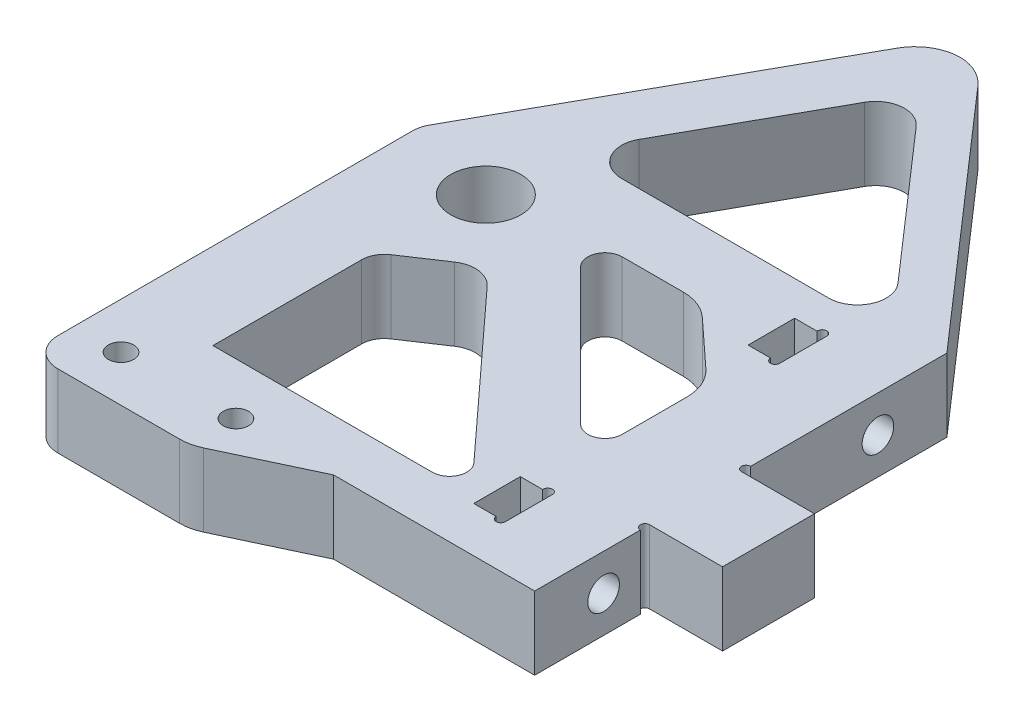
SolidWorks part; units mm, degrees
material "6061 Alloy"
ref_plane "Front Plane" through (0, 0, 0) normal (0, 0, 1) x (1, 0, 0)
ref_plane "Top Plane" through (0, 0, 0) normal (0, 1, 0) x (1, 0, 0)
ref_plane "Right Plane" through (0, 0, 0) normal (1, 0, 0) x (0, 0, -1)
sketch "Sketch1" plane through (0, 0, 0) normal (0, 1, 0) x (1, 0, 0)
  line L1 (-80, 0) -> (-80, 60)
  line L8 (-52, -8) -> (-80, -8)
  line L9 (-80, -8) -> (-80, 0)
  line L10 (-80, 60) -> (-48, 117.5)
  line L11 (-48, 117.5) -> (-40, 117.5)
  line L12 (-40, 117.5) -> (0, 71.75)
  line L14 (0, 36) -> (12.7, 36)
  line L15 (12.7, 36) -> (12.7, 20)
  line L16 (12.7, 20) -> (0, 20)
  line L18 (0, 18.4) -> (0, 0)
  line L19 (0, 71.75) -> (0, 37.6)
  line L20 (-52, -8) -> (-35, 0)
  line L21 (-35, 0) -> (0, 0)
  circle A0 centre (-64, 55.5) radius 6.1
  circle A3 centre (-72, 0) radius 2.2
  circle A4 centre (-52, 0) radius 2.2
  arc A5 (0, 20) -> (0, 18.4) centre (0, 19.2) ccw
  arc A6 (0, 36) -> (0, 37.6) centre (0, 36.8) cw
  point P23 (12.7, 28)
  dimension "D8" = 12.2
  dimension "D19" = 0.8
  dimension "D20" = 0.8
  dimension "D12" = 4.4
  dimension "D16" = 4.4
  dimension "D1" = 80
  dimension "D2" = 71.75
  dimension "D3" = 60
  dimension "D9" = 16
  dimension "D14" = 8
  dimension "D15" = 20
  dimension "D10" = 8
  dimension "D13" = 8
  dimension "D17" = 55.5
  dimension "D4" = 57.5
  dimension "D5" = 32
  dimension "D6" = 8
  dimension "D18" = 12.7
  dimension "D7" = 28
  dimension "D11" = 16
  dimension "D21" = 35
extrude "Boss-Extrude1" add sketch "Sketch1" along normal blind 12.7
fillet "Fillet1" radius 8 2 edges at (-40, 6.35, -117.5) (-48, 6.35, -117.5)
sketch "Sketch3" plane through (0, 12.7, 0) normal (0, 1, 0) x (1, 0, 0)
  line L5 (-7.5496, 69.75) -> (-41.5119, 108.5944)
  line L6 (-41.5119, 108.5944) -> (-63.1296, 69.75)
  line L7 (-63.1296, 69.75) -> (-7.5496, 69.75)
  line L10 (0, 71.75) -> (-37.6094, 114.7657) construction
  line L11 (-50.2871, 113.3903) -> (-80, 60) construction
  line L16 (-80, 60) -> (-80, -8) construction
  line L17 (-65, 37) -> (-65, 9)
  line L18 (-53, 45) -> (-65, 37)
  line L20 (-42.7574, 58) -> (-32.1279, 58)
  line L21 (-26.7016, 55.8784) -> (-18.5738, 48.3758)
  line L22 (-16, 42.4974) -> (-16, 31.2426)
  line L23 (-21.1213, 29.1213) -> (-44.8787, 52.8787)
  line L25 (-53, 45) -> (-20, 9)
  line L26 (-20, 9) -> (-65, 9)
  arc A4 (-21.1213, 29.1213) -> (-16, 31.2426) centre (-19, 31.2426) ccw
  arc A5 (-44.8787, 52.8787) -> (-42.7574, 58) centre (-42.7574, 55) cw
  arc A6 (-16, 42.4974) -> (-18.5738, 48.3758) centre (-24, 42.4974) ccw
  arc A7 (-26.7016, 55.8784) -> (-32.1279, 58) centre (-32.1279, 50) ccw
  point P19 (-16, 24)
  point P21 (-16, 58)
  point P23 (-50, 58)
  point P24 (-50, 58)
  point P27 (-16, 24)
  point P30 (-24, 8)
  point P31 (-16, 46)
  point P34 (-29, 58)
  point P36 (-58, 42)
  dimension "D14" = 15
  dimension "D8" = 3
  dimension "D9" = 8
  dimension "D15" = 45
  dimension "D1" = 7
  dimension "D2" = 10
  dimension "D3" = 10
  dimension "D4" = 7
  dimension "D5" = 2
  dimension "D6" = 22
  dimension "D7" = 13
  dimension "D10" = 64
  dimension "D11" = 32
  dimension "D12" = 34
  dimension "D13" = 34
  dimension "D16" = 36
  dimension "D17" = 28
  dimension "D18" = 12
extrude "Cut-Extrude1" cut sketch "Sketch3" against normal through all
fillet "Fillet2" radius 5 3 edges at (-41.5119, 6.35, -108.5944) (-7.5496, 6.35, -69.75) (-63.1296, 6.35, -69.75)
sketch "Sketch4" plane through (0, 12.7, 0) normal (0, 1, 0) x (1, 0, 0)
  line L0 (0, 0) -> (0, 18.4) construction
  line L2 (-18.5, 16) -> (-18.5, 7.9)
  line L4 (-13, 16.1) -> (-13, 7.9)
  line L5 (-18.5, 16) -> (-14.5937, 16)
  line L6 (-18.5, 7.9) -> (-14.6, 7.9)
  line L7 (-18.5, 55.65) -> (-14.6, 55.65)
  line L8 (-13, 63.85) -> (-13, 55.65)
  line L9 (-18.5, 63.75) -> (-14.5937, 63.75)
  line L10 (-18.5, 63.75) -> (-18.5, 55.65)
  arc A0 (-13, 16.1) -> (-14.5937, 16) centre (-13.8, 16.1) ccw
  arc A1 (-13, 7.9) -> (-14.6, 7.9) centre (-13.8, 7.9) cw
  arc A2 (-13, 55.65) -> (-14.6, 55.65) centre (-13.8, 55.65) cw
  arc A3 (-13, 63.85) -> (-14.5937, 63.75) centre (-13.8, 63.85) ccw
  point P4 (-13, 12)
  point P12 (-13, 59.75)
  dimension "D5" = 0.8
  dimension "D2" = 13
  dimension "D3" = 8.2
  dimension "D4" = 5.5
  dimension "D7" = 12
  dimension "D1" = 12
  dimension "D6" = 2
extrude "Cut-Extrude2" cut sketch "Sketch4" against normal through all
sketch "Sketch6" plane through (-13, 0, 0) normal (-1, 0, 0) x (0, 0, 1)
  line L0 (-7.9, 0) -> (-7.9, 12.7) construction
  line L1 (-7.9, 12.7) -> (-16.1, 12.7) construction
  line L2 (-55.65, 0) -> (-55.65, 12.7) construction
  circle A0 centre (-12, 6.35) radius 2.75
  circle A1 centre (-59.75, 6.35) radius 2.75
  dimension "D2" = 5.5
  dimension "D5" = 5.5
  dimension "D1" = 4.1
  dimension "D3" = 6.35
  dimension "D4" = 4.1
extrude "Cut-Extrude3" cut sketch "Sketch6" against normal through all
fillet "Fillet4" radius 5 2 edges at (-80, 6.35, 8) (-80, 6.35, -60)
fillet "Fillet5" radius 8 1 edges at (-52, 6.35, 8)
fillet "Fillet6" radius 3 1 edges at (-20, 6.35, -9)
fillet "Fillet7" radius 5 1 edges at (-53, 6.35, -45)
fillet "Fillet8" radius 4 1 edges at (-65, 6.35, -37)
equation "\"DriveMotorLength\"= 90mm"
equation "\"DriveMotorGap\"= 10mm"
equation "\"AluminumThickness\"= 0.5in"
equation "\"ChassisWidth\"= ( \"DriveMotorLength\" + \"AluminumThickness\" ) * 2 + \"DriveMotorGap\""
equation "\"RepeatMagnumHoleWidth\"= 19.05mm"
equation "\"MortiseWidth\"= 16mm"
equation "\"ChassisScrewThruHole\"= 5.5mm"
equation "\"MortiseSlotWidth\"= 16.2mm"
equation "\"Dogbone\"= 0.8mm"
equation "\"D19@Sketch1\"=\"Dogbone\""
equation "\"D20@Sketch1\"=\"Dogbone\""
equation "\"D5@Sketch4\"=\"Dogbone\""
equation "\"D2@Sketch6\"=\"ChassisScrewThruHole\""
equation "\"D5@Sketch6\"=\"ChassisScrewThruHole\""
equation "\"D11@Sketch1\"=\"MortiseWidth\""
